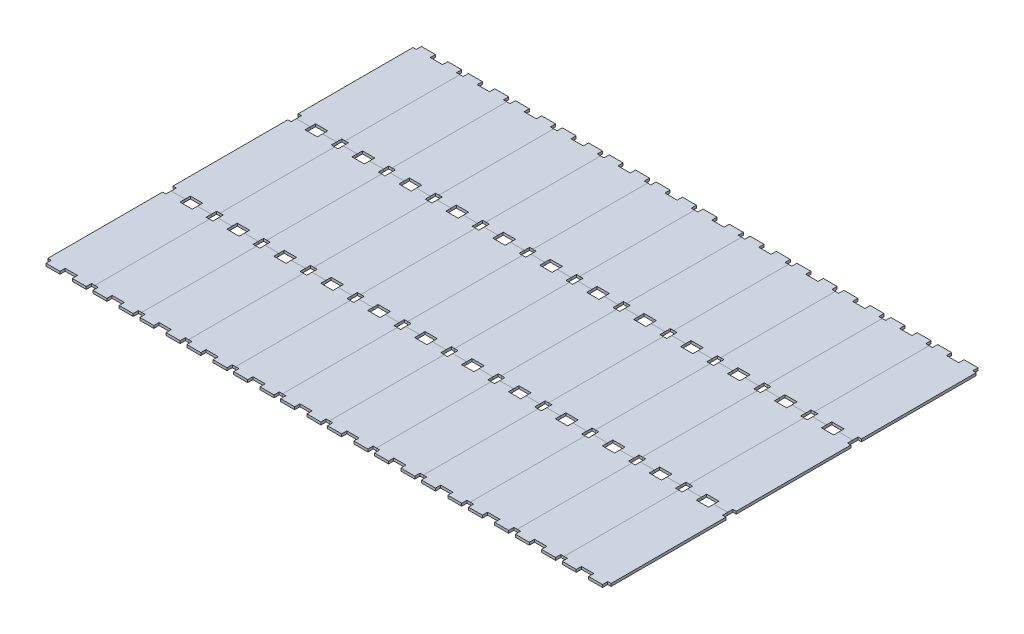
SolidWorks part; units mm, degrees
material "Cedar"
ref_plane "Front Plane" through (0, 0, 0) normal (0, 0, 1) x (1, 0, 0)
ref_plane "Top Plane" through (0, 0, 0) normal (0, 1, 0) x (1, 0, 0)
ref_plane "Right Plane" through (0, 0, 0) normal (1, 0, 0) x (0, 0, -1)
sketch "Sketch1" plane through (0, 0, 0) normal (0, 1, 0) x (1, 0, 0)
  line L1 (-28.575, 76.2) -> (28.575, 76.2)
  line L2 (-28.575, 76.2) -> (-28.575, -76.2)
  line L3 (-28.575, -76.2) -> (28.575, -76.2)
  line L4 (28.575, 76.2) -> (28.575, -76.2)
  line L5 (-28.575, 76.2) -> (28.575, -76.2) construction
  line L6 (-28.575, -76.2) -> (28.575, 76.2) construction
  point P0 (0, 0)
  dimension "D1" = 57.15
  dimension "D2" = 152.4
extrude "Boss-Extrude1" add sketch "Sketch1" along normal blind 3.175
sketch "Sketch2" plane through (0, 3.175, 0) normal (0, 1, 0) x (1, 0, 0)
  line L0 (-28.575, -69.85) -> (28.575, -69.85) construction
  line L1 (-28.575, 76.2) -> (-28.575, -76.2) construction
  line L2 (28.575, -76.2) -> (28.575, 76.2) construction
  line L3 (0, -76.2) -> (0, -69.85) construction
  line L4 (-28.575, -76.2) -> (28.575, -76.2) construction
  line L5 (-24.505, -69.85) -> (-28.575, -69.85)
  line L6 (-24.505, -69.85) -> (-7.495, -69.85) construction
  line L7 (-24.505, -69.85) -> (-24.505, -76.2)
  line L8 (-24.505, -76.2) -> (-7.495, -76.2) construction
  line L9 (-7.495, -69.85) -> (-7.495, -76.2)
  line L10 (-24.505, -69.85) -> (-7.495, -76.2) construction
  line L11 (-24.505, -76.2) -> (-7.495, -69.85) construction
  line L12 (-28.575, -69.85) -> (-28.575, -76.2)
  line L13 (-28.575, -76.2) -> (-24.505, -76.2)
  line L14 (-7.495, -76.2) -> (7.495, -76.2)
  line L15 (0, -76.2) -> (0, -69.85)
  line L16 (7.495, -69.85) -> (-7.495, -69.85)
  line L17 (24.505, -76.2) -> (7.495, -69.85) construction
  line L18 (24.505, -69.85) -> (7.495, -76.2) construction
  line L19 (24.505, -76.2) -> (7.495, -76.2) construction
  line L20 (24.505, -69.85) -> (7.495, -69.85) construction
  line L21 (28.575, -76.2) -> (24.505, -76.2)
  line L22 (28.575, -69.85) -> (28.575, -76.2)
  line L23 (7.495, -69.85) -> (7.495, -76.2)
  line L24 (24.505, -69.85) -> (24.505, -76.2)
  line L25 (24.505, -69.85) -> (28.575, -69.85)
  point P10 (-16, -73.025)
  point P22 (16, -73.025)
  line M12 (28.575, -76.2) -> (28.575, 76.2)
  line M14 (-28.575, 76.2) -> (-28.575, -76.2)
  line M15 (-28.575, -76.2) -> (28.575, -76.2)
  dimension "D1" = 6.35
  dimension "D2" = 7.495
  dimension "D3" = 17.01
extrude "Cut-Extrude1" cut sketch "Sketch2" against normal through all contours L7 L5 M14 M15 | L15 L16 L9 M15 | L23 L16 L15 L14 | L25 L24 M15 M12 region at (-26.54, 3.175, 73.025) region at (26.54, 3.175, 73.025) region at (-3.7475, 3.175, 73.025) region at (3.7475, 3.175, 73.025)
mirror "Mirror1" about plane through (0, 0, 0) normal (0, 0, 1) of "Cut-Extrude1"
pattern_linear "LPattern1" count 12 spacing 57.15 along (1, 0, 0) count 3 spacing 152.4 along (0, 0, 1) of bodies 103
